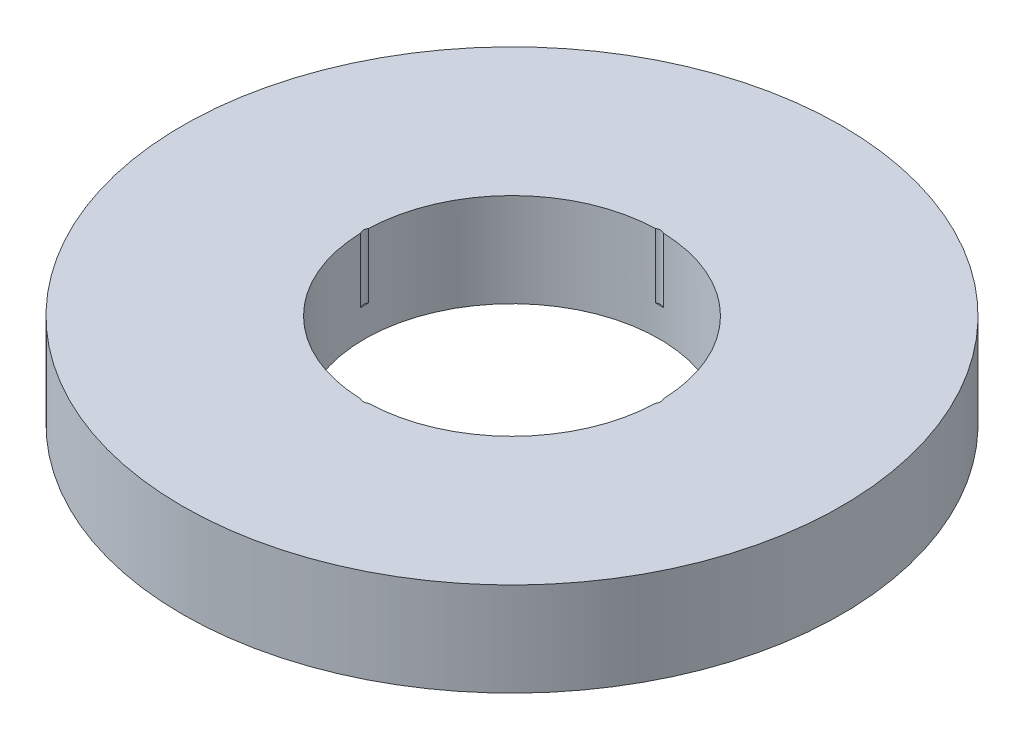
SolidWorks part; units mm, degrees
ref_plane "Front Plane" through (0, 0, 0) normal (0, 0, 1) x (1, 0, 0)
ref_plane "Top Plane" through (0, 0, 0) normal (0, 1, 0) x (1, 0, 0)
ref_plane "Right Plane" through (0, 0, 0) normal (1, 0, 0) x (0, 0, -1)
sketch "Sketch1" plane through (0, 0, 0) normal (0, 1, 0) x (1, 0, 0)
  circle A0 centre (0, 0) radius 95
  dimension "FLANGE_OD" = 190
extrude "Boss-Extrude1" add sketch "Sketch1" along normal blind 27
sketch "Sketch2" plane through (0, 0, 0) normal (0, 1, 0) x (1, 0, 0)
  circle A0 centre (0, 0) radius 42.5
  dimension "BORE_D" = 85
extrude "Cut-Extrude1" cut sketch "Sketch2" along normal through all
sketch "Sketch3" plane through (0, 27, 0) normal (0, 1, 0) x (1, 0, 0)
  circle A0 centre (0, 0) radius 40.8823 construction
  circle A1 centre (-40.8823, 0) radius 1.9736
  dimension "BOLT_D" = 3.9471
  dimension "BOLT_PCD" = 81.7646
extrude "Cut-Extrude2" cut sketch "Sketch3" against normal blind 18.5885
pattern_circular "CirPattern1" count 4 over 360 about axis through (0, 0, 0) along (0, 1, 0) of "Cut-Extrude2"
